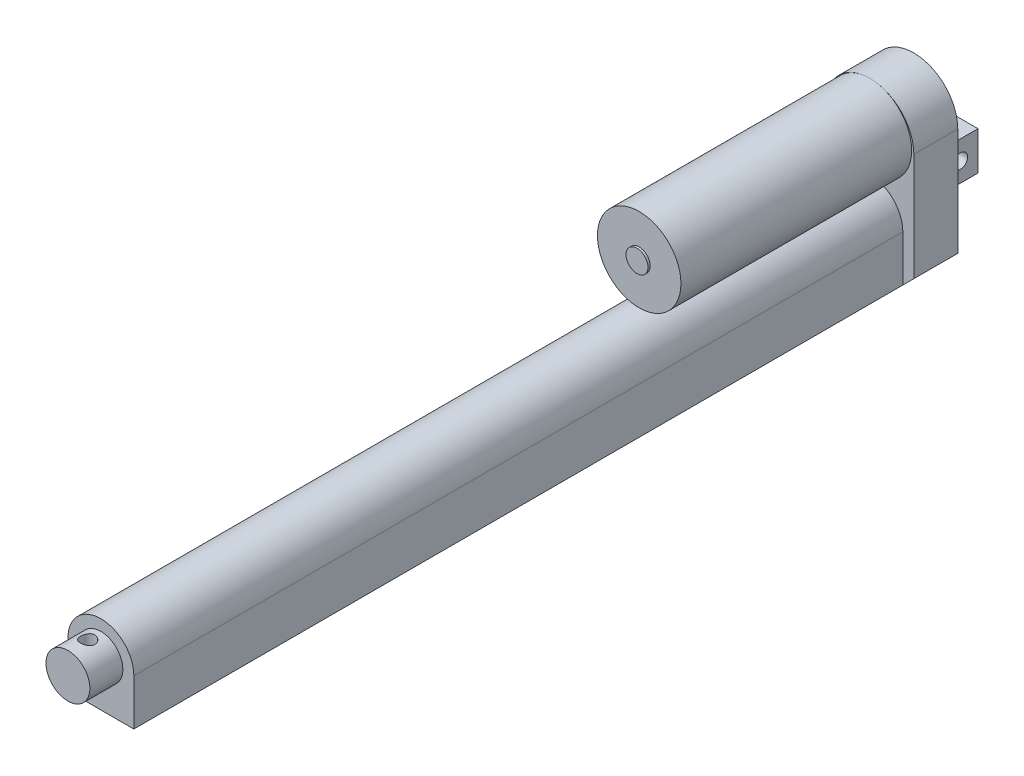
SolidWorks part; units mm, degrees
ref_plane "Front Plane" through (0, 0, 0) normal (0, 0, 1) x (1, 0, 0)
ref_plane "Top Plane" through (0, 0, 0) normal (0, 1, 0) x (1, 0, 0)
ref_plane "Right Plane" through (0, 0, 0) normal (1, 0, 0) x (0, 0, -1)
sketch "Sketch1" plane through (0, 0, 0) normal (0, 0, 1) x (1, 0, 0)
  line L1 (-20, -37) -> (20, -37)
  line L2 (-20, -37) -> (-20, 37)
  line L3 (-20, 37) -> (20, 37)
  line L4 (20, -37) -> (20, 37)
  line L5 (-20, -37) -> (20, 37) construction
  line L6 (-20, 37) -> (20, -37) construction
  point P0 (0, 0)
  dimension "D1" = 74
  dimension "D2" = 40
extrude "Boss-Extrude1" add sketch "Sketch1" along normal blind 20
fillet "Fillet1" 2 edges at (20, 37, 10) (-20, 37, 10) type full round first side face at (20, 0, 10) second side face at (-20, 0, 10) middle face at (0, 37, 10)
chamfer "Chamfer1" distance 5 angle 45 1 edges at (-20, -37, 10)
chamfer "Chamfer2" distance 5 angle 45 1 edges at (20, -37, 10)
sketch "Sketch2" plane through (0, 0, 20) normal (0, 0, 1) x (1, 0, 0)
  circle A0 centre (0, 18.023) radius 19
  dimension "D1" = 38
extrude "Boss-Extrude2" add sketch "Sketch2" along normal blind 105
sketch "Sketch3" plane through (0, 0, 125) normal (0, 0, 1) x (1, 0, 0)
  circle A0 centre (0, 18.023) radius 5
  circle A1 centre (0, 18.023) radius 19 construction
  dimension "D1" = 10
extrude "Boss-Extrude3" add sketch "Sketch3" along normal blind 1
sketch "Sketch5" plane through (0, 0, 20) normal (0, 0, 1) x (1, 0, 0)
  line L0 (-15, -37) -> (15, -37)
  line L1 (-15, -37) -> (-15, -1)
  line L2 (15, -37) -> (15, -1)
  line L3 (-15, -1) -> (15, -1)
  dimension "D1" = 36
extrude "Boss-Extrude4" add sketch "Sketch5" along normal blind 350
fillet "Fillet2" 2 edges at (-15, -1, 195) (15, -1, 195) type full round first side face at (-15, -19, 195) second side face at (15, -19, 195) middle face at (0, -1, 195)
sketch "Sketch6" plane through (0, 0, 370) normal (0, 0, 1) x (1, 0, 0)
  circle A0 centre (0, -16) radius 10
  dimension "D1" = 20
extrude "Boss-Extrude5" add sketch "Sketch6" along normal blind 15
ref_plane "Plane1" through (0, -25, 0) normal (0, 1, 0) x (1, 0, 0)
sketch "Sketch8" plane through (0, -25, 0) normal (0, 1, 0) x (1, 0, 0)
  line L0 (-10, -385) -> (15.7221, -385) construction
  circle A1 centre (0, -376) radius 3.25
  point P0 (0, -376)
  dimension "D1" = 9
  dimension "D2" = 6.5
extrude "Cut-Extrude1" cut sketch "Sketch8" against normal through all both and the other way through all contours A1
sketch "Sketch9" plane through (0, 0, 0) normal (0, 0, -1) x (-1, 0, 0)
  line L0 (0, 37) -> (23.7824, 37) construction
  line L2 (-10.2086, 2.75) -> (7.2914, 2.75)
  line L3 (-10.2086, 2.75) -> (-10.2086, -14.75)
  line L4 (-10.2086, -14.75) -> (7.2914, -14.75)
  line L5 (7.2914, 2.75) -> (7.2914, -14.75)
  line L6 (-10.2086, 2.75) -> (7.2914, -14.75) construction
  line L7 (-10.2086, -14.75) -> (7.2914, 2.75) construction
  arc A0 (20, 17) -> (-20, 17) centre (0, 17) ccw construction
  point P0 (-1.4586, -6)
  point P6 (-1.4586, -6)
  dimension "D1" = 43
  dimension "D2" = 17.5
  dimension "D3" = 17.5
extrude "Boss-Extrude6" add sketch "Sketch9" along normal blind 19
sketch "Sketch10" plane through (0, 0, 0) normal (0, 1, 0) x (1, 0, 0)
  line L0 (-7.2914, 19) -> (-7.2914, 0) construction
  line L1 (-7.2914, 19) -> (10.2086, 19) construction
  circle A0 centre (1.4586, 11) radius 3.25
  dimension "D1" = 6.5
  dimension "D2" = 8.75
  dimension "D3" = 8
sketch "Sketch11" plane through (10.2086, 0, 0) normal (1, 0, 0) x (0, 0, -1)
  line L0 (19, 2.75) -> (19, -14.75) construction
  line L1 (19, 2.75) -> (0, 2.75) construction
  circle A0 centre (11, -6) radius 3.25
  dimension "D2" = 6.5
  dimension "D1" = 8
  dimension "D3" = 8.75
extrude "Cut-Extrude3" cut sketch "Sketch11" against normal through all
